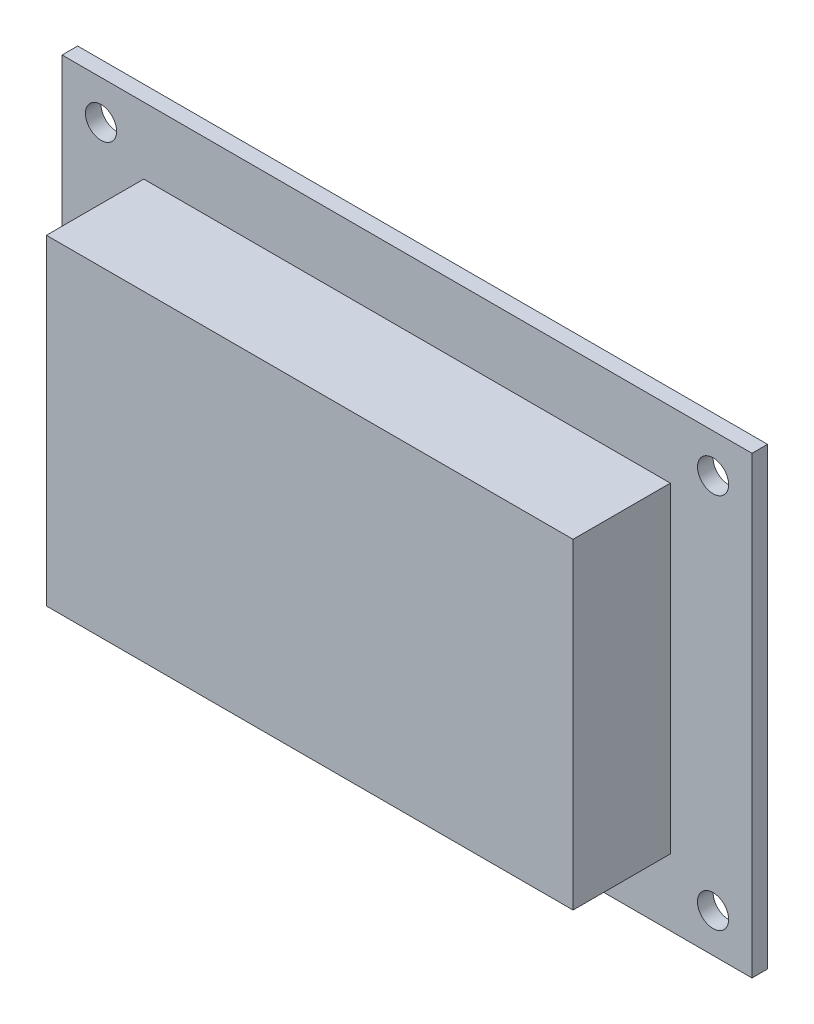
SolidWorks part; units mm, degrees
ref_plane "Plano frontal" through (0, 0, 0) normal (0, 0, 1) x (1, 0, 0)
ref_plane "Plano superior" through (0, 0, 0) normal (0, 1, 0) x (1, 0, 0)
ref_plane "Plano direito" through (0, 0, 0) normal (1, 0, 0) x (0, 0, -1)
sketch "Esboço1" plane through (0, 0, 0) normal (0, 0, 1) x (1, 0, 0)
  line L0 (-11.2515, 0) -> (0, 0) construction
  line L1 (-35.45, 23.35) -> (35.45, 23.35)
  line L2 (-35.45, 23.35) -> (-35.45, -23.35)
  line L3 (-35.45, -23.35) -> (35.45, -23.35)
  line L4 (35.45, 23.35) -> (35.45, -23.35)
  line L5 (-35.45, 23.35) -> (35.45, -23.35) construction
  line L6 (-35.45, -23.35) -> (35.45, 23.35) construction
  line L7 (0, 0) -> (0, 10.1302) construction
  circle A0 centre (-31.45, 19.35) radius 1.6
  circle A1 centre (31.45, 19.35) radius 1.6
  circle A2 centre (31.45, -19.35) radius 1.6
  circle A3 centre (-31.45, -19.35) radius 1.6
  point P0 (0, 0)
  dimension "D3" = 3.2
  dimension "D1" = 70.9
  dimension "D2" = 46.7
  dimension "D4" = 4
  dimension "D5" = 4
extrude "Ressalto-extrusão1" add sketch "Esboço1" along normal blind 1.6
sketch "Esboço2" plane through (0, 0, 1.6) normal (0, 0, 1) x (1, 0, 0)
  line L1 (-27.0602, 16.5001) -> (27.0602, 16.5001)
  line L2 (-27.0602, 16.5001) -> (-27.0602, -16.5001)
  line L3 (-27.0602, -16.5001) -> (27.0602, -16.5001)
  line L4 (27.0602, 16.5001) -> (27.0602, -16.5001)
  line L5 (-27.0602, 16.5001) -> (27.0602, -16.5001) construction
  line L6 (-27.0602, -16.5001) -> (27.0602, 16.5001) construction
  point P0 (0, 0)
extrude "Ressalto-extrusão2" add sketch "Esboço2" along normal blind 10
equation "\"D5@Esboço1\"=\"D4@Esboço1\""
